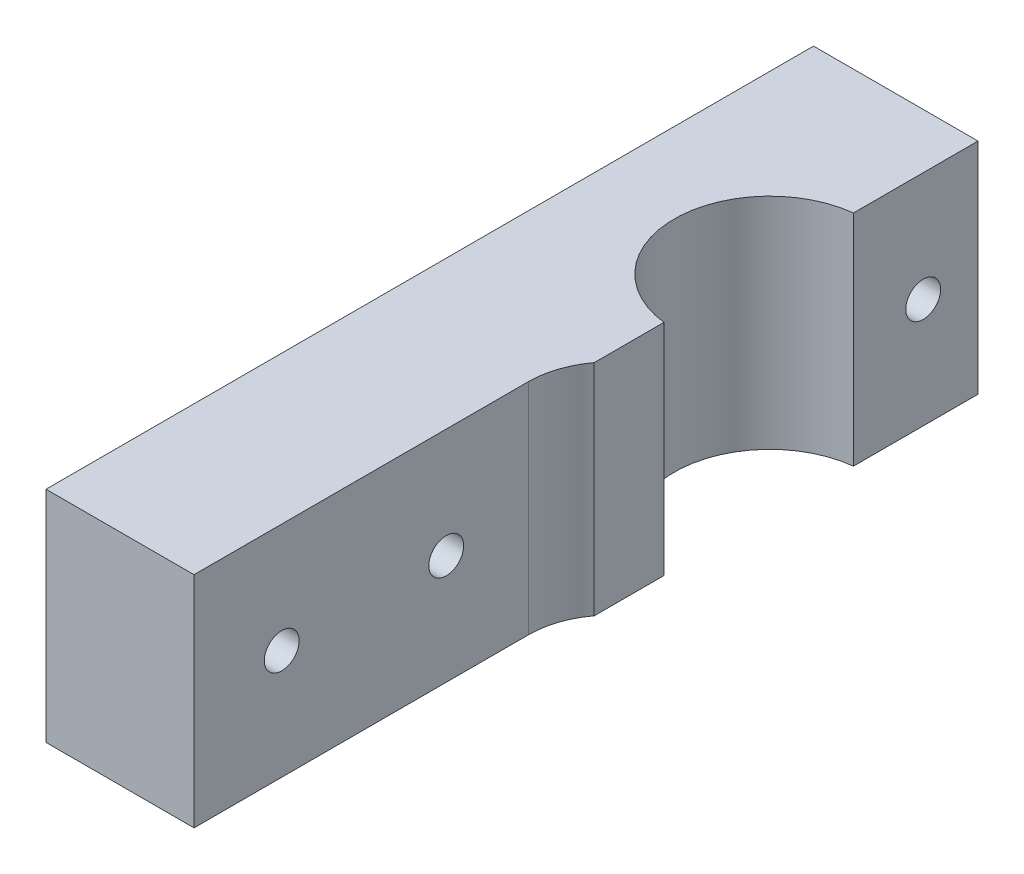
SolidWorks part; units mm, degrees
material "6061 Alloy"
ref_plane "Front" through (0, 0, 0) normal (0, 0, 1) x (1, 0, 0)
ref_plane "Top" through (0, 0, 0) normal (0, 1, 0) x (1, 0, 0)
ref_plane "Right" through (0, 0, 0) normal (1, 0, 0) x (0, 0, -1)
sketch "Sketch1" plane through (0, 0, 0) normal (0, 1, 0) x (1, 0, 0)
  line L0 (-1.27, 10.9758) -> (-1.27, 25.4)
  line L1 (-1.27, 25.4) -> (-20.32, 25.4)
  line L2 (-1.27, 25.4) -> (-1.27, -63.5) construction
  line L3 (-1.27, -63.5) -> (-20.32, -63.5)
  line L4 (-20.32, 25.4) -> (-20.32, -63.5)
  line L5 (-1.27, -10.9758) -> (-1.27, -63.5)
  arc A0 (-1.27, 10.9758) -> (-1.27, -10.9758) centre (0, 0) ccw
  circle A1 centre (0, 0) radius 11.049 construction
  dimension "D2" = 22.098
  dimension "D1" = 25.4
  dimension "D3" = 19.05
  dimension "D4" = 1.27
  dimension "D5" = 63.5
extrude "Boss-Extrude1" add sketch "Sketch1" along normal mid plane 25.4
sketch "Sketch4" plane through (-20.32, 0, 0) normal (-1, 0, 0) x (0, 0, 1)
  line L0 (63.5, 12.7) -> (63.5, -12.7) construction
  point P0 (-19.05, 0)
  point P1 (34.29, 0)
  point P2 (53.34, 0)
  dimension "D1" = 19.05
  dimension "D2" = 10.16
  dimension "D3" = 19.05
hole_wizard "CBORE for #10 Binding Head Machine Screw1" [suppressed] positions "Sketch5" profile "Sketch6" counterbore size "#10" standard "ANSI Inch"
sketch "Sketch5" plane through (-20.32, 0, 0) normal (-1, 0, 0) x (0, 0, 1)
  point P0 (-19.05, 0)
  point P3 (34.29, 0)
  point P6 (53.34, 0)
sketch "Sketch6" plane through (-20.32, 0, -19.05) normal (0, 1, 0) x (0, 0, 1)
  line L0 (0, 0) -> (0, 509.5338)
  line L1 (0, 509.5338) -> (2.5527, 508)
  line L2 (2.5527, 508) -> (2.5527, 3.1242)
  line L3 (2.5527, 3.1242) -> (5.5562, 3.1242)
  line L4 (5.5562, 3.1242) -> (5.5562, 0)
  line L5 (5.5562, 0) -> (0, 0)
  line L10 (0, 509.5338) -> (-2.5527, 508) construction
  line L11 (0, -6.35) -> (0, 107.95) construction
  dimension "Hole Dia." = 5.1054
  dimension "Hole Depth" = 508
  dimension "C'Bore Dia." = 11.1125
  dimension "C'Bore Depth" = 3.1242
  dimension "Drill Angle" = 118
sketch "Sketch7" plane through (0, 12.7, 0) normal (0, 1, 0) x (1, 0, 0)
  line L1 (-1.27, -63.5) -> (-3.175, -63.5)
  line L2 (-1.27, -63.5) -> (-1.27, -19.05)
  line L3 (-1.27, -19.05) -> (-3.175, -19.05)
  line L4 (-3.175, -63.5) -> (-3.175, -19.05)
  dimension "D1" = 3.175
  dimension "D2" = 44.45
extrude "Cut-Extrude1" cut sketch "Sketch7" against normal through all
fillet "Fillet1" radius 9.525 1 edges at (-3.175, 0, 19.05)
hole_wizard "#10-32 Tapped Hole1" positions "Sketch8" profile "Sketch9" tap size "#10-32" standard "ANSI Inch"
sketch "Sketch8" plane through (-3.175, 0, 0) normal (1, 0, 0) x (0, 0, -1)
  point P0 (-53.34, 0)
  point P3 (-34.29, 0)
  point P6 (19.05, 0)
sketch "Sketch9" plane through (-3.175, 0, 53.34) normal (0, 1, 0) x (0, 0, -1)
  line L0 (0, 0) -> (0, 15.6913)
  line L1 (0, 15.6913) -> (2.0193, 14.478)
  line L2 (2.0193, 14.478) -> (2.0193, 0)
  line L5 (2.0193, 0) -> (0, 0)
  line L10 (0, 15.6913) -> (-2.0193, 14.478) construction
  line L11 (0, -6.35) -> (0, 107.95) construction
  dimension "Tap Drill Dia." = 4.0386
  dimension "Tap Drill Depth" = 14.478
  dimension "Drill Angle" = 118
cosmetic thread "Hole Thread1" parameters "D1"=12.192, "D2"=4.826
cosmetic thread "Hole Thread2" parameters "D1"=12.192, "D2"=4.826
hole_wizard "#10-32 Tapped Hole2" positions "Sketch10" profile "Sketch11" tap size "#10-32" standard "ANSI Inch"
sketch "Sketch10" plane through (-1.27, 0, 0) normal (1, 0, 0) x (0, 0, -1)
  point P0 (19.05, 0)
sketch "Sketch11" plane through (-1.27, 0, -19.05) normal (0, 1, 0) x (0, 0, -1)
  line L0 (0, 0) -> (0, 15.6913)
  line L1 (0, 15.6913) -> (2.0193, 14.478)
  line L2 (2.0193, 14.478) -> (2.0193, 0)
  line L5 (2.0193, 0) -> (0, 0)
  line L10 (0, 15.6913) -> (-2.0193, 14.478) construction
  line L11 (0, -6.35) -> (0, 107.95) construction
  dimension "Tap Drill Dia." = 4.0386
  dimension "Tap Drill Depth" = 14.478
  dimension "Drill Angle" = 118
cosmetic thread "Hole Thread3" parameters "D1"=12.192, "D2"=4.826
